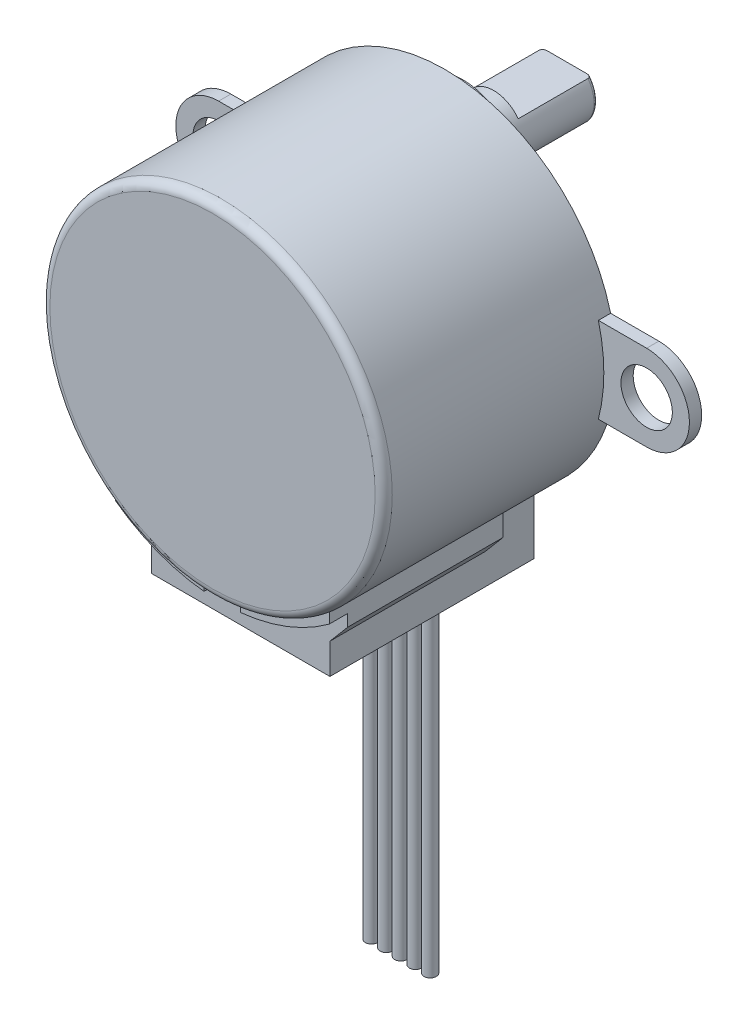
SolidWorks part; units mm, degrees
ref_plane "Ön Düzlem" through (0, 0, 0) normal (0, 0, 1) x (1, 0, 0)
ref_plane "Üst Düzlem" through (0, 0, 0) normal (0, 1, 0) x (1, 0, 0)
ref_plane "Sağ Düzlem" through (0, 0, 0) normal (1, 0, 0) x (0, 0, -1)
sketch "Sketch1" plane through (0, 0, 0) normal (0, 0, 1) x (1, 0, 0)
  circle A0 centre (0, 0) radius 14
extrude "Boss-Extrude1" add sketch "Sketch1" along normal blind 19
sketch "Sketch2" plane through (0, 0, 0) normal (0, 0, -1) x (-1, 0, 0)
  circle A0 centre (0, 8) radius 4.5
  point P0 (0, 8)
extrude "Boss-Extrude2" add sketch "Sketch2" along normal blind 1.5
sketch "Sketch3" plane through (0, 0, -1.5) normal (0, 0, -1) x (-1, 0, 0)
  circle A0 centre (0, 8) radius 2.5
extrude "Boss-Extrude3" add sketch "Sketch3" along normal blind 2.5
sketch "Sketch5" plane through (0, 0, -4) normal (0, 0, -1) x (-1, 0, 0)
  line L1 (-2, 9.5) -> (2, 9.5)
  line L3 (-2, 6.5) -> (2, 6.5)
  arc A0 (2, 6.5) -> (2, 9.5) centre (0, 8) ccw
  arc A1 (-2, 9.5) -> (-2, 6.5) centre (0, 8) ccw
extrude "Boss-Extrude5" add sketch "Sketch5" along normal blind 6
fillet "Fillet1" radius 0.3 2 edges at (-2.5, 8, -10) (2.5, 8, -10)
fillet "Fillet2" radius 0.7 1 edges at (14, 0, 19)
sketch "Sketch6" plane through (0, 0, 0) normal (0, 0, -1) x (-1, 0, 0)
  line L0 (0, 3.5) -> (0, -3.5268) construction
  line L1 (-17.5, 3.5) -> (-13.5554, 3.5)
  line L3 (17.5, -3.5) -> (13.5554, -3.5)
  line L4 (-13.5554, -3.5) -> (-17.5, -3.5)
  line L5 (13.5554, 3.5) -> (17.5, 3.5)
  arc A0 (-17.5, 3.5) -> (-17.5, -3.5) centre (-17.5, 0) ccw
  circle A1 centre (-17.5, 0) radius 2.1
  circle A2 centre (0, 8) radius 4.5 construction
  circle A3 centre (0, 8) radius 4.5 construction
  arc A4 (17.5, 3.5) -> (17.5, -3.5) centre (17.5, 0) cw
  circle A5 centre (17.5, 0) radius 2.1
  arc A6 (13.5554, -3.5) -> (13.5554, 3.5) centre (0, 0) ccw
  arc A7 (-13.5554, 3.5) -> (-13.5554, -3.5) centre (0, 0) ccw
  dimension "D1" = 7
  dimension "D2" = 17.5
extrude "Boss-Extrude6" add sketch "Sketch6" against normal blind 1
sketch "Sketch7" plane through (0, 0, 0) normal (0, 0, -1) x (-1, 0, 0)
  line L2 (-7.3, -11.9461) -> (-7.3, -17)
  line L3 (-7.3, -17) -> (7.3, -17)
  line L4 (7.3, -11.9461) -> (7.3, -17)
  arc A0 (-7.3, -11.9461) -> (7.3, -11.9461) centre (0, 0) ccw
  dimension "D1" = 17
  dimension "D2" = 14.6
extrude "Boss-Extrude7" add sketch "Sketch7" against normal blind 16.7
sketch "Sketch8" plane through (0, 0, 16.7) normal (0, 0, 1) x (1, 0, 0)
  line L0 (-7.3, -14.5) -> (-8.75, -12.785)
  line L1 (-7.3, -14.5) -> (-7.3, -11.9461)
  line L2 (-8.75, -10.9287) -> (-8.75, -12.785)
  line L4 (8.75, -10.9287) -> (8.75, -12.785)
  line L9 (8.75, -12.785) -> (7.3, -14.5)
  line L10 (7.3, -11.9461) -> (7.3, -14.5)
  arc A0 (-8.75, -10.9287) -> (-7.3, -11.9461) centre (0, 0) ccw
  arc A1 (7.3, -11.9461) -> (8.75, -10.9287) centre (0, 0) ccw
  dimension "D1" = 17.5
extrude "Boss-Extrude8" add sketch "Sketch8" against normal blind 12.7
sketch "Sketch9" plane through (0, 0, -10) normal (0, 0, -1) x (-1, 0, 0)
  circle A0 centre (0, 8) radius 0.4315
extrude "Cut-Extrude1" cut sketch "Sketch9" against normal blind 0.3
sketch "Sketch10" plane through (0, 0, 16.7) normal (0, 0, 1) x (1, 0, 0)
  line L0 (-8.75, -11.8122) -> (-8.75, -10.9287)
  line L2 (-1.5, -13.9194) -> (-1.5, -14.6233)
  line L4 (1.5, -13.9194) -> (1.5, -14.6233)
  line L7 (8.75, -10.9287) -> (8.75, -11.8122)
  arc A0 (-8.75, -11.8122) -> (-1.5, -14.6233) centre (0, 0) ccw
  arc A1 (-8.75, -10.9287) -> (-1.5, -13.9194) centre (0, 0) ccw
  arc A2 (1.5, -14.6233) -> (8.75, -11.8122) centre (0, 0) ccw
  arc A3 (1.5, -13.9194) -> (8.75, -10.9287) centre (0, 0) ccw
  dimension "D1" = 3
extrude "Boss-Extrude10" add sketch "Sketch10" along normal blind 1.5
sketch "Sketch11" plane through (0, -17, 0) normal (0, -1, 0) x (1, 0, 0)
  line L0 (7.3, 0) -> (-7.3, 0) construction
  line L1 (-3.75, 4.2) -> (3.75, 4.2)
  line L2 (-3.75, 4.2) -> (-3.75, 3)
  line L3 (-3.75, 3) -> (3.75, 3)
  line L4 (3.75, 4.2) -> (3.75, 3)
  dimension "D1" = 7.5
  dimension "D2" = 1.2
  dimension "D3" = 3.75
  dimension "D4" = 3
extrude "Cut-Extrude2" cut sketch "Sketch11" against normal blind 2
sketch "Sketch12" plane through (0, -15, 0) normal (0, -1, 0) x (1, 0, 0)
  line L0 (-3.75, 3.6) -> (3.75, 3.6) construction
  line L1 (-3.75, 4.2) -> (-3.75, 3) construction
  line L2 (3.75, 3) -> (3.75, 4.2) construction
  line L3 (0, 3.6) -> (0, 1.54) construction
  circle A0 centre (-2.4, 3.6) radius 0.5
  circle A1 centre (-1.2, 3.6) radius 0.5
  circle A2 centre (0, 3.6) radius 0.5
  circle A3 centre (1.2, 3.6) radius 0.5
  circle A4 centre (2.4, 3.6) radius 0.5
  dimension "D1" = 1.2
  dimension "D2" = 1.2
extrude "Boss-Extrude11" add sketch "Sketch12" along normal blind 32
